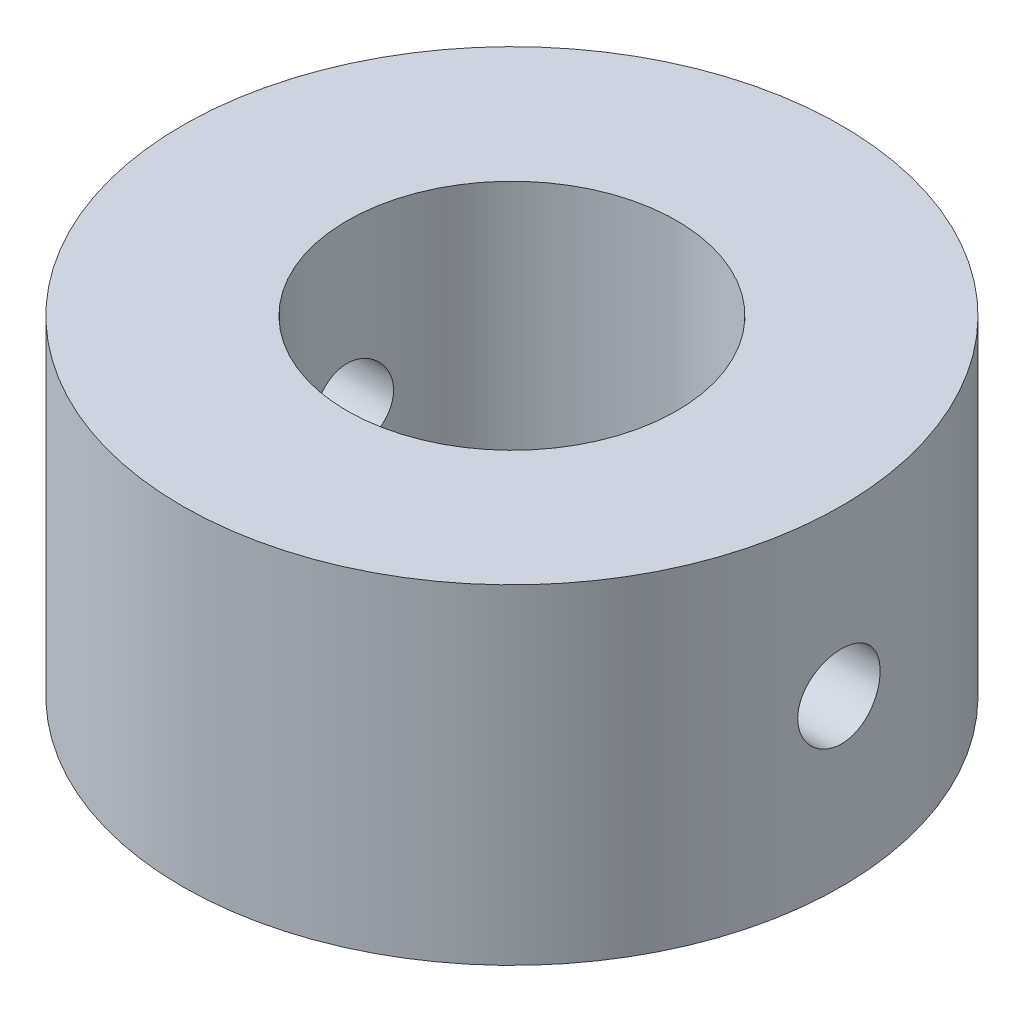
SolidWorks part; units mm, degrees
ref_plane "Front Plane" through (0, 0, 0) normal (0, 0, 1) x (1, 0, 0)
ref_plane "Top Plane" through (0, 0, 0) normal (0, 1, 0) x (1, 0, 0)
ref_plane "Right Plane" through (0, 0, 0) normal (1, 0, 0) x (0, 0, -1)
sketch "Sketch1" plane through (0, 0, 0) normal (0, 1, 0) x (1, 0, 0)
  circle A0 centre (0, 0) radius 16
  circle A1 centre (0, 0) radius 8
  dimension "D1" = 32
  dimension "D2" = 16
extrude "Boss-Extrude1" add sketch "Sketch1" along normal blind 16
sketch "Sketch2" plane through (0, 0, 0) normal (1, 0, 0) x (0, 0, -1)
  circle A0 centre (0, 8) radius 2
  dimension "D2" = 4
  dimension "D1" = 8
extrude "Cut-Extrude1" cut sketch "Sketch2" against normal blind 16 and the other way blind 16
